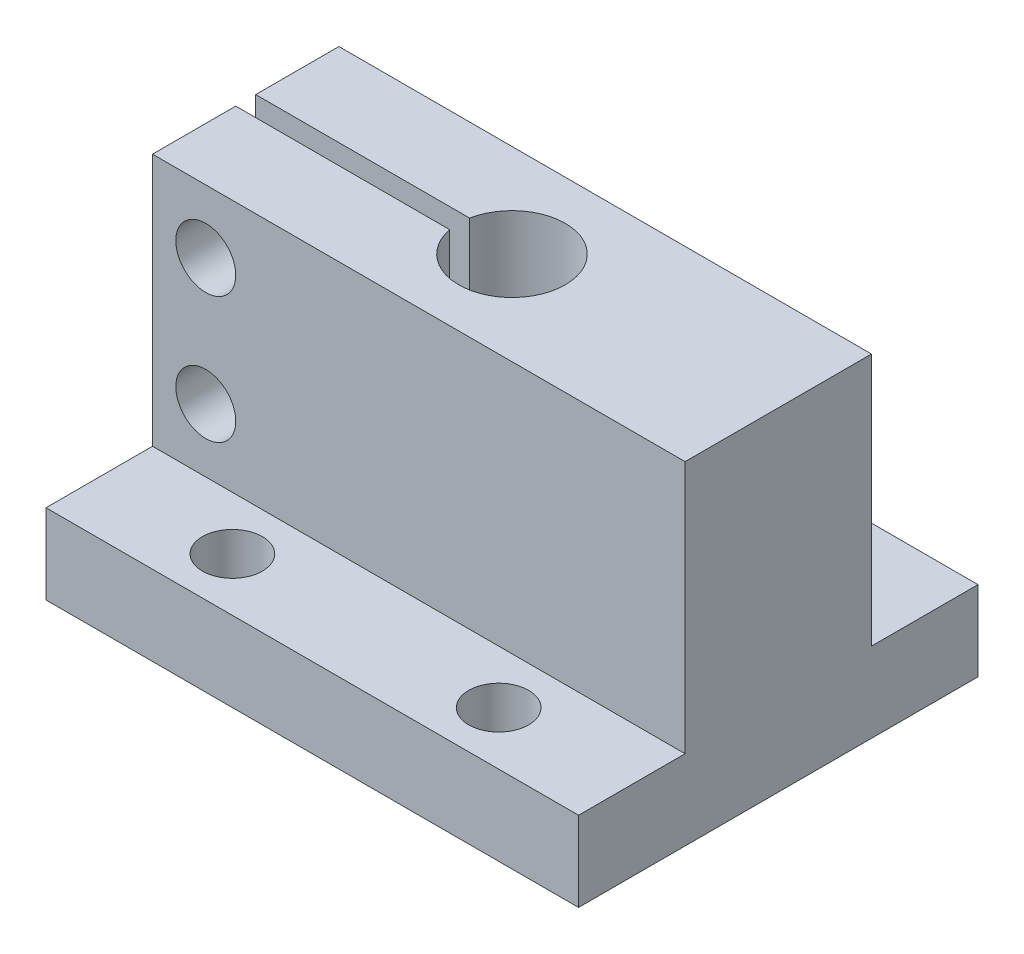
SolidWorks part; units mm, degrees
material "6061-T6 (SS)"
ref_plane "Front Plane" through (0, 0, 0) normal (0, 0, 1) x (1, 0, 0)
ref_plane "Top Plane" through (0, 0, 0) normal (0, 1, 0) x (1, 0, 0)
ref_plane "Right Plane" through (0, 0, 0) normal (1, 0, 0) x (0, 0, -1)
sketch "Sketch2" plane through (0, 0, 0) normal (0, 1, 0) x (1, 0, 0)
  line L0 (0, -7) -> (0, -15) construction
  line L1 (20, 15) -> (-20, 15)
  line L2 (20, 15) -> (20, -15)
  line L3 (20, -15) -> (-20, -15)
  line L4 (-20, 15) -> (-20, -15)
  line L5 (20, 15) -> (-20, -15) construction
  line L6 (20, -15) -> (-20, 15) construction
  line L7 (20, 7) -> (-20, 7)
  line L8 (20, 7) -> (20, -7)
  line L9 (20, -7) -> (-20, -7)
  line L10 (-20, 7) -> (-20, -7)
  line L11 (20, 7) -> (-20, -7) construction
  line L12 (20, -7) -> (-20, 7) construction
  line L13 (0, -11) -> (-20, -11) construction
  line L14 (-20, -11) -> (20, -11) construction
  line L15 (-10, -11) -> (-10, -15) construction
  line L16 (-10, -15) -> (-10, -7) construction
  line L17 (10, -15) -> (10, -7) construction
  line L18 (0, 0) -> (-20, 0) construction
  line L19 (-20, 0) -> (20, 0) construction
  line L20 (-20, 11) -> (20, 11) construction
  line L21 (-10, 15) -> (-10, 7) construction
  line L22 (10, 15) -> (10, 7) construction
  circle A0 centre (0, 0) radius 4
  circle A1 centre (-10, -11) radius 2.25
  circle A2 centre (10, -11) radius 2.25
  circle A3 centre (10, 11) radius 2.25
  circle A4 centre (-10, 11) radius 2.25
  point P0 (0, 0)
  dimension "D3" = 8
  dimension "D5" = 4.5
  dimension "D1" = 40
  dimension "D2" = 30
  dimension "D4" = 8
extrude "Boss-Extrude_wall" add sketch "Sketch2" along normal blind 25 contours L9 L2 L7 L4 A0 region at (19.5762, 0, 0)
extrude "Boss-Extrude2" add sketch "Sketch2<3>" along normal blind 6 contours L2 L9 L4 L3 A1 A2 | L7 L2 L1 L4 A3 A4 region at (0, 0, -11) region at (0, 0, 11)
sketch "Sketch2<3>" plane through (0, 0, 0) normal (0, 1, 0) x (1, 0, 0) same geometry as "Sketch2"
sketch "Sketch3" plane through (0, 25, 0) normal (0, 1, 0) x (1, 0, 0)
  line L0 (0, 0) -> (-20, 0) construction
  line L1 (-20, 7) -> (-20, -7) construction
  line L3 (0, 0.75) -> (-20, 0.75)
  line L4 (0, 0.75) -> (0, -0.75)
  line L5 (0, -0.75) -> (-20, -0.75)
  line L6 (-20, 0.75) -> (-20, -0.75)
  line L7 (0, 0.75) -> (-20, -0.75) construction
  line L8 (0, -0.75) -> (-20, 0.75) construction
  point P5 (-10, 0)
  dimension "D1" = 1.5
extrude "Cut-Extrude1" cut sketch "Sketch3" against normal through all
sketch "Sketch4" plane through (0, 0, 7) normal (0, 0, 1) x (1, 0, 0)
  line L0 (-12, 25) -> (-12, 6) construction
  line L1 (20, 25) -> (-20, 25) construction
  line L2 (20, 6) -> (-20, 6) construction
  line L3 (-20, 25) -> (-20, 6) construction
  line L4 (-20, 15.5) -> (-12, 15.5) construction
  line L5 (-12, 20.25) -> (-20, 20.25) construction
  line L6 (-12, 10.75) -> (-20, 10.75) construction
  circle A0 centre (-16, 20.25) radius 2.25
  circle A1 centre (-16, 10.75) radius 2.25
  dimension "D4" = 4.5
  dimension "D1" = 8
  dimension "D2" = 9.5
  dimension "D3" = 4.75
extrude "Cut-Extrude2" cut sketch "Sketch4" against normal through all
equation "\"____ GENERATED PART EXPORTS ____\" = 0"
equation "\"SYS_VersionTag\" = 2"
equation "\"SHB_PlanLength\" = 40mm"
equation "\"SHB_PlanWidth\" = 30mm"
equation "\"SHB_Height\" = 25mm"
equation "\"SHB_BoreDia\" = 8mm"
equation "\"SHB_SplitClampSlotWidth\" = 1.5mm"
equation "\"SHB_ClampPitch\" = 24mm"
equation "\"SHB_ClampClearDia\" = 4.5mm"
equation "\"SHB_ClampScrewCount\" = 2"
equation "\"D1@Sketch2\"=\"SHB_PlanLength\""
equation "\"D2@Sketch2\"=\"SHB_PlanWidth\""
equation "\"D3@Sketch2\"=\"SHB_BoreDia\""
equation "\"D1@Boss-Extrude_wall\" = \"SHB_Height\""
equation "\"D1@Boss-Extrude2\"=6"
equation "\"D1@Sketch3\"=\"SHB_SplitClampSlotWidth\""
equation "\"D3@Sketch4\"=4.75"
